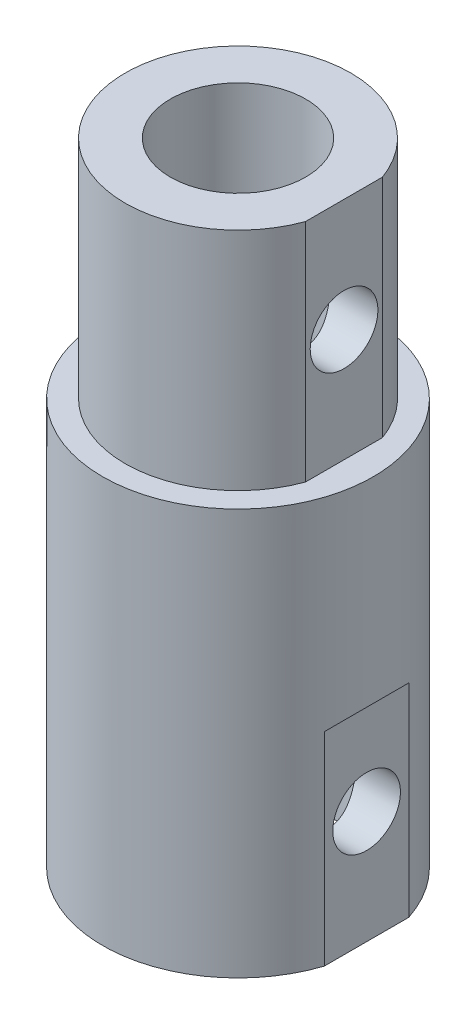
SolidWorks part; units mm, degrees
material "1060 Alloy"
ref_plane "Front Plane" through (0, 0, 0) normal (0, 0, 1) x (1, 0, 0)
ref_plane "Top Plane" through (0, 0, 0) normal (0, 1, 0) x (1, 0, 0)
ref_plane "Right Plane" through (0, 0, 0) normal (1, 0, 0) x (0, 0, -1)
sketch "Sketch1" plane through (0, 0, 0) normal (0, 1, 0) x (1, 0, 0)
  circle A0 centre (0, 0) radius 4
  circle A1 centre (0, 0) radius 6
  dimension "D1" = 8
  dimension "D2" = 12
extrude "Boss-Extrude1" add sketch "Sketch1" along normal blind 10
sketch "Sketch2" plane through (0, 10, 0) normal (0, 1, 0) x (1, 0, 0)
  circle A0 centre (0, 0) radius 6
extrude "Boss-Extrude2" add sketch "Sketch2" along normal blind 8
sketch "Sketch3" plane through (0, 18, 0) normal (0, 1, 0) x (1, 0, 0)
  circle A0 centre (0, 0) radius 5
  circle A1 centre (0, 0) radius 3
  dimension "D1" = 10
  dimension "D2" = 6
extrude "Boss-Extrude3" add sketch "Sketch3" along normal blind 10
sketch "Sketch4" plane through (0, 0, 0) normal (1, 0, 0) x (0, 0, -1)
  line L0 (-6, 0) -> (6, 0) construction
  line L1 (5, 28) -> (-5, 28) construction
  circle A0 centre (0, 5) radius 1.5
  circle A1 centre (0, 23) radius 1.5
  dimension "D1" = 3
  dimension "D2" = 3
  dimension "D3" = 5
  dimension "D4" = 5
extrude "Cut-Extrude1" cut sketch "Sketch4" along normal blind 10
sketch "Sketch5" plane through (0, 0, 0) normal (0, -1, 0) x (1, 0, 0)
  line L0 (6, 0) -> (5.7, 0) construction
  line L1 (5.7, -3.5893) -> (5.7, 2.9388)
  line L2 (5.7, -3.5893) -> (7.0647, -3.5893)
  line L3 (5.7, 2.9388) -> (7.0647, 2.9388)
  line L4 (7.0647, -3.5893) -> (7.0647, 2.9388)
  circle A0 centre (0, 0) radius 6 construction
  dimension "D1" = 0.3
extrude "Cut-Extrude2" cut sketch "Sketch5" against normal blind 10
chamfer "Chamfer1" distance 1 angle 45 1 edges at (5.7, 10, 0)
sketch "Sketch6" plane through (0, 28, 0) normal (0, 1, 0) x (1, 0, 0)
  line L0 (5, 0) -> (4.7, 0) construction
  line L1 (4.7, -2.3032) -> (4.7, 2.3986)
  line L2 (4.7, -2.3032) -> (5.6532, -2.3032)
  line L3 (4.7, 2.3986) -> (5.6532, 2.3986)
  line L4 (5.6532, -2.3032) -> (5.6532, 2.3986)
  circle A0 centre (0, 0) radius 5 construction
  circle A1 centre (0, 0) radius 5 construction
  dimension "D1" = 0.3
extrude "Cut-Extrude3" cut sketch "Sketch6" against normal blind 10
